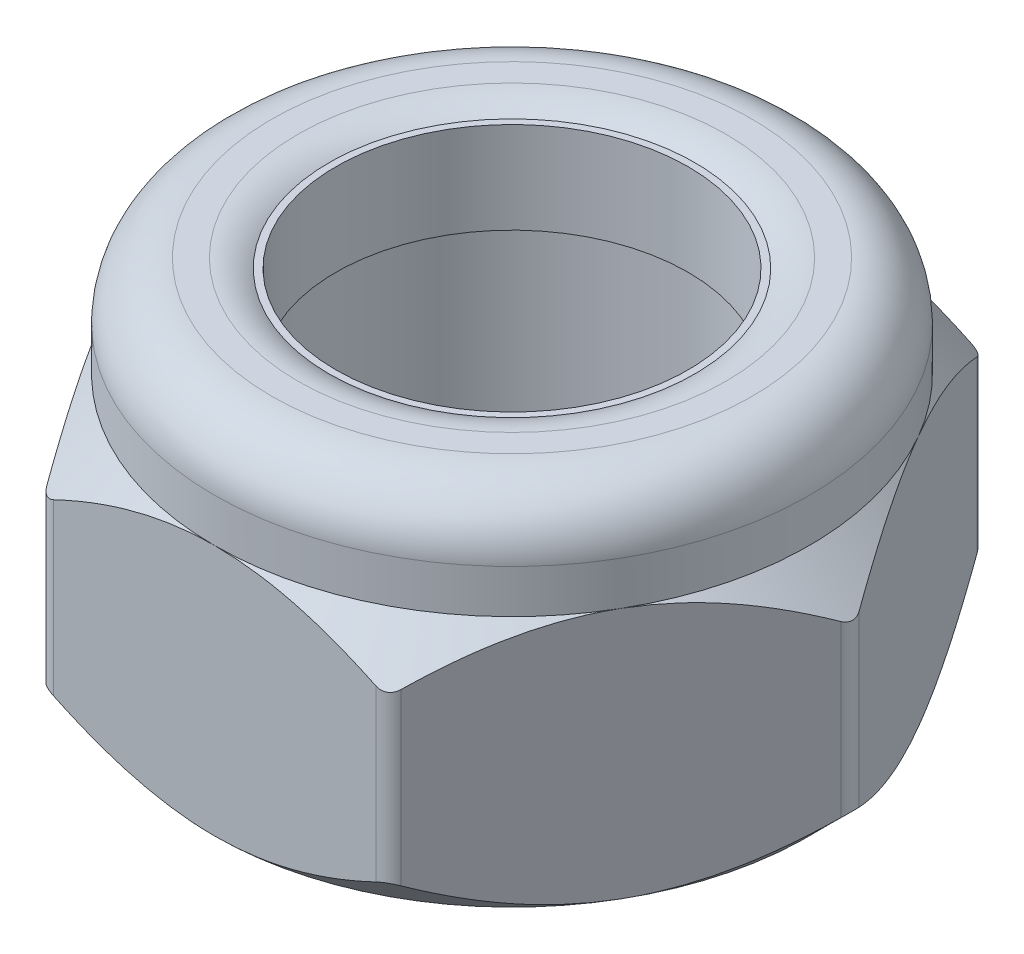
SolidWorks part; units mm, degrees
material "铸造碳钢"
ref_plane "Front" through (0, 0, 0) normal (0, 0, 1) x (1, 0, 0)
ref_plane "Top" through (0, 0, 0) normal (0, 1, 0) x (1, 0, 0)
ref_plane "Right" through (0, 0, 0) normal (1, 0, 0) x (0, 0, -1)
other "配置表"
sketch "草图1" plane through (0, 0, 0) normal (0, 1, 0) x (1, 0, 0)
  line L1 (7.5056, 0) -> (3.7528, 6.5)
  line L2 (3.7528, 6.5) -> (-3.7528, 6.5)
  line L3 (-3.7528, 6.5) -> (-7.5056, 0)
  line L4 (-7.5056, 0) -> (-3.7528, -6.5)
  line L5 (-3.7528, -6.5) -> (3.7528, -6.5)
  line L6 (3.7528, -6.5) -> (7.5056, 0)
  circle A0 centre (0, 0) radius 6.5 construction
  dimension "六角对边长" = 13
extrude "凸台-拉伸1" add sketch "草图1" along normal mid plane 5.5
sketch "草图3" plane through (0, 2.75, 0) normal (0, 1, 0) x (1, 0, 0)
  circle A0 centre (0, 0) radius 6.5
  dimension "圆形外直径" = 13
extrude "凸台-拉伸2" add sketch "草图3" along normal blind 2.2
sketch "草图4" plane through (0, 4.95, 0) normal (0, 1, 0) x (1, 0, 0)
  circle A0 centre (0, 0) radius 4
  dimension "螺母内径" = 8
extrude "切除-拉伸1" cut sketch "草图4" against normal through all
sketch "草图5" plane through (0, 4.95, 0) normal (0, 1, 0) x (1, 0, 0)
  circle A0 centre (0, 0) radius 4
  circle A1 centre (0, 0) radius 3.85
  dimension "橡胶内径" = 7.7
  dimension "橡皮圈外直径" = 8
extrude "凸台-拉伸3" add sketch "草图5" against normal up to surface (2 mm away) from offset 0.2 up to face at (-6.5449, 2.75, 0) offset against normal yes
fillet "圆角1" radius 1.25 2 edges at (0, 4.95, 4) (0, 4.95, 6.5)
sketch "草图6" plane through (0, 0, 0) normal (0, 0, 1) x (1, 0, 0)
  line L0 (0, -1000) -> (0, 49000) construction
  line L1 (-1000, 0) -> (49000, 0) construction
  line L2 (-7.5056, 2.75) -> (-7.5056, 1.7444)
  line L3 (-7.5056, 1.7444) -> (-6.5, 2.75)
  line L4 (-6.5, 2.75) -> (-7.5056, 2.75)
  line L5 (0, 2.75) -> (-5.6292, 2.75) construction
  line L6 (-7.5056, 2.75) -> (-7.5056, -2.75) construction
  line L7 (-6.5, -998.4247) -> (-6.5, 49001.5753) construction
  line L8 (-6.5, 3.7) -> (-6.5, 2.75) construction
  line L9 (-7.5056, -2.75) -> (-7.5056, -1.7444)
  line L10 (-7.5056, -1.7444) -> (-6.5, -2.75)
  line L11 (-6.5, -2.75) -> (-7.5056, -2.75)
  dimension "D1" = 45
revolve "切除-旋转1" cut sketch "草图6" angle 360 about L0
fillet "圆角3" radius 0.4 6 edges at (-7.5056, 0, 0) (-3.7528, 0, -6.5) (3.7528, 0, -6.5) (7.5056, 0, 0) (3.7528, 0, 6.5) (-3.7528, 0, 6.5)
move or copy body "实体-移动/复制1" [suppressed] bodies to move or copy 105
move or copy body "实体-移动/复制2" [suppressed] bodies to move or copy 105
